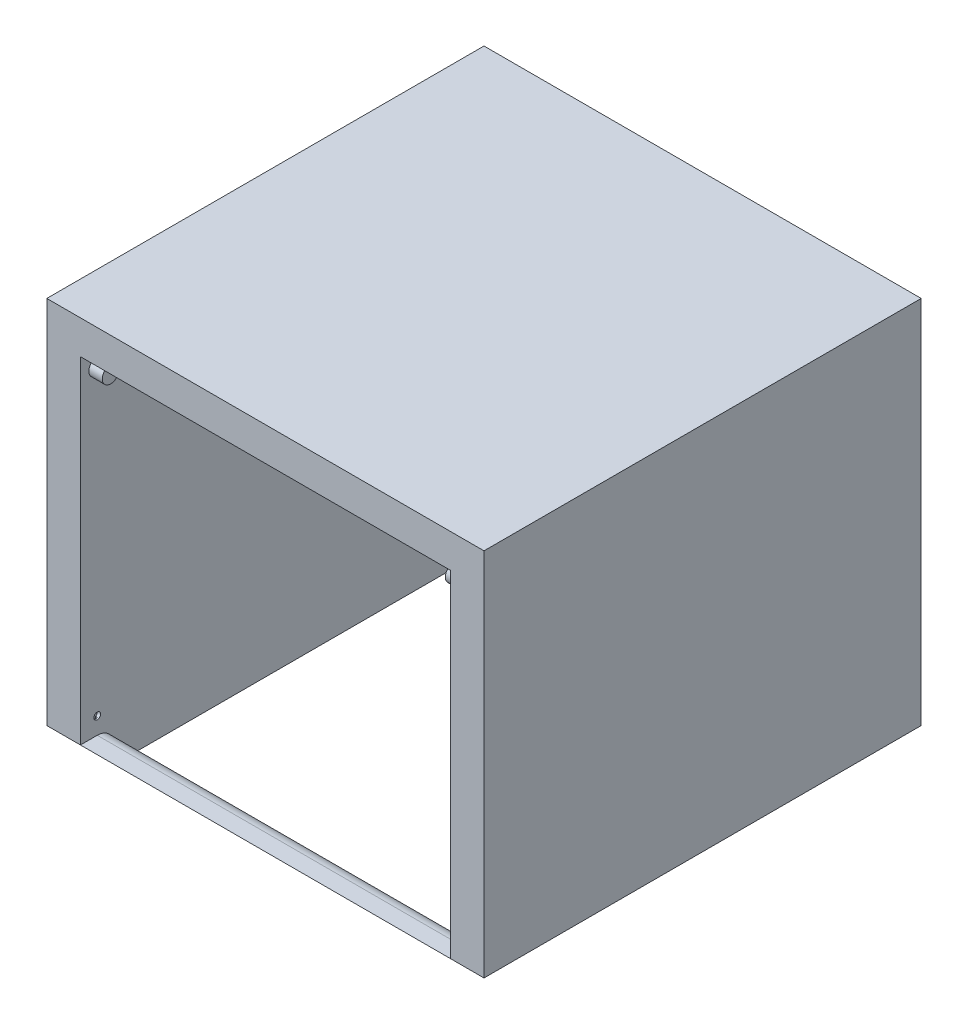
SolidWorks part; units mm, degrees
ref_plane "Front Plane" through (0, 0, 0) normal (0, 0, 1) x (1, 0, 0)
ref_plane "Top Plane" through (0, 0, 0) normal (0, 1, 0) x (1, 0, 0)
ref_plane "Right Plane" through (0, 0, 0) normal (1, 0, 0) x (0, 0, -1)
sketch "Sketch1" plane through (0, 0, 0) normal (0, 1, 0) x (1, 0, 0)
  line L0 (-325, 325) -> (-325, -325)
  line L1 (225, 225) -> (-225, 225)
  line L2 (225, 225) -> (225, -225)
  line L3 (225, -225) -> (-225, -225)
  line L4 (-225, 225) -> (-225, -225)
  line L5 (225, 225) -> (-225, -225) construction
  line L6 (225, -225) -> (-225, 225) construction
  line L7 (325, -325) -> (-325, -325)
  line L8 (325, 325) -> (325, -325)
  line L9 (325, 325) -> (-325, 325)
  point P0 (0, 0)
  dimension "D1" = 450
  dimension "D2" = 450
  dimension "D3" = 100
extrude "Boss-Extrude2" add sketch "Sketch1" against normal blind 103 draft 45
sketch "Sketch5" plane through (0, 0, 0) normal (0, 1, 0) x (1, 0, 0)
  line L0 (-275, -275) -> (-275, 275)
  line L1 (-225, -225) -> (225, -225)
  line L2 (-225, -225) -> (-225, 225)
  line L3 (-225, 225) -> (225, 225)
  line L4 (225, -225) -> (225, 225)
  line L5 (-275, 275) -> (275, 275)
  line L6 (275, -275) -> (275, 275)
  line L7 (-275, -275) -> (275, -275)
  dimension "D1" = 50
extrude "Cut-Extrude2" cut sketch "Sketch5" against normal blind 103
sketch "Sketch7" plane through (0, 0, 0) normal (0, 1, 0) x (1, 0, 0)
  line L0 (-275, 275) -> (-275, -325)
  line L1 (-325, -325) -> (-275, -325)
  line L2 (-325, -325) -> (-325, 325)
  line L3 (-325, 325) -> (325, 325)
  line L4 (325, -325) -> (325, 325)
  line L5 (275, 275) -> (-275, 275)
  line L9 (275, 275) -> (275, -325)
  line L10 (275, -325) -> (325, -325)
extrude "Boss-Extrude3" add sketch "Sketch7" along normal blind 500
sketch "Sketch8" plane through (0, 500, 0) normal (0, 1, 0) x (1, 0, 0)
  line L1 (-325, -325) -> (325, -325)
  line L2 (-325, -325) -> (-325, 325)
  line L3 (-325, 325) -> (325, 325)
  line L4 (325, -325) -> (325, 325)
extrude "Boss-Extrude4" add sketch "Sketch8" along normal blind 50
fillet "Fillet1" radius 25 1 edges at (0, 0, 275)
sketch "Sketch9" plane through (-275, 0, 0) normal (1, 0, 0) x (0, 0, -1)
  line L0 (-325, 500) -> (-275, 450) construction
  line L1 (-325, 550) -> (-325, 0) construction
  circle A0 centre (-300, 475) radius 12.5
  dimension "D3" = 25
  dimension "D1" = 50
  dimension "D2" = 45
extrude "Boss-Extrude5" add sketch "Sketch9" along normal blind 20
mirror "Mirror1" about plane through (0, 0, 0) normal (1, 0, 0) of "Boss-Extrude5"
sketch "Sketch10" plane through (-275, 0, 0) normal (1, 0, 0) x (0, 0, -1)
  line L0 (-325, 0) -> (-275, 50) construction
  line L1 (-325, 500) -> (-325, 0) construction
  line L2 (-300, 25) -> (-325, 25) construction
  line L3 (-325, 550) -> (-325, 0) construction
  circle A0 centre (-300, 25) radius 5
  dimension "D3" = 10
  dimension "D1" = 45
  dimension "D2" = 50
extrude "Cut-Extrude3" cut sketch "Sketch10" against normal blind 5
sketch "Sketch11" plane through (0, 0, 0) normal (0, 1, 0) x (1, 0, 0)
  line L0 (-325, -325) -> (-280, -325) construction
  line L1 (-325, -325) -> (-275, -325) construction
  line L2 (-280, -325) -> (-280, -300) construction
  line L3 (-280, -300) -> (-280, -302.5) construction
  line L5 (-280, -302.5) -> (-277.5, -302.5)
  line L6 (-280, -302.5) -> (-280, -297.5)
  line L7 (-280, -297.5) -> (-277.5, -297.5)
  line L8 (-277.5, -302.5) -> (-277.5, -297.5)
  dimension "D1" = 45
  dimension "D2" = 25
  dimension "D3" = 2.5
  dimension "D4" = 5
  dimension "D5" = 2.5
extrude "Cut-Extrude4" cut sketch "Sketch11" against normal through all
extrude "Cut-Extrude5" cut sketch "Sketch11<2>" along normal blind 25
sketch "Sketch11<2>" plane through (0, 0, 0) normal (0, 1, 0) x (1, 0, 0) same geometry as "Sketch11"
sketch "Sketch13" plane through (0, 0, -275) normal (0, 0, 1) x (1, 0, 0)
  line L0 (-275, 0) -> (275, 0) construction
  line L1 (-275, 500) -> (-270, 500)
  line L2 (-275, 500) -> (-275, 0)
  line L3 (-275, 0) -> (-270, 0)
  line L4 (-270, 500) -> (-270, 0)
  dimension "D1" = 5
extrude "Cut-Extrude6" cut sketch "Sketch13" against normal blind 5
sketch "Sketch14" plane through (0, -162.5, 162.5) normal (0, -0.7071, 0.7071) x (1, 0, 0)
  line L0 (-302.5, 197.9899) -> (-297.5, 190.9188)
  line L1 (-280, 197.9899) -> (-302.5, 197.9899)
  line L2 (-280, 197.9899) -> (-280, 190.9188)
  line L3 (-280, 190.9188) -> (-297.5, 190.9188)
extrude "Cut-Extrude7" cut sketch "Sketch14" against normal blind 2.5
sketch "Sketch18" plane through (-162.5, -162.5, 0) normal (-0.7071, -0.7071, 0) x (0, 0, 1)
  line L0 (302.5, 197.9899) -> (297.5, 190.9188)
  line L1 (-275, 190.9188) -> (-275, 197.9899)
  line L3 (297.5, 190.9188) -> (-275, 190.9188)
  line L4 (302.5, 197.9899) -> (-275, 197.9899)
extrude "Cut-Extrude11" cut sketch "Sketch18" against normal blind 2.5
sketch "Sketch19" plane through (-280, 0, 0) normal (-1, 0, 0) x (0, 0, 1)
  line L0 (297.5, -23.9645) -> (295.7322, -25.7322)
  line L1 (295.7322, -25.7322) -> (297.5, -27.5)
  line L2 (297.5, -27.5) -> (297.5, -23.9645)
extrude "Cut-Extrude12" cut sketch "Sketch19" against normal blind 2.5
fillet "Fillet2" radius 1.25 1 edges at (-278.75, -23.9645, 297.5)
fillet "Fillet3" radius 1.25 2 edges at (-280, -21.6161, 301.6161) (-280, -22.5314, 298.9331)
fillet "Fillet4" radius 1.25 1 edges at (-298.2322, -23.2322, 298.2322)
sketch "Sketch22" plane through (-140, 140, 0) normal (0.7071, -0.7071, 0) x (0, 0, -1)
  line L1 (-302.5, -229.8097) -> (-299.8483, -229.8097)
  line L2 (-302.5, -229.8097) -> (-302.5, -227.3097)
  line L3 (-302.5, -227.3097) -> (-299.8483, -227.3097)
  line L4 (-299.8483, -229.8097) -> (-299.8483, -227.3097)
extrude "Boss-Extrude6" add sketch "Sketch22" against normal blind 2.5
sketch "Sketch23" plane through (0, 140, 140) normal (0, -0.7071, -0.7071) x (1, 0, 0)
  line L0 (-281.25, 227.3097) -> (-299.8483, 227.3097) construction
  line L1 (-302.5, 229.8097) -> (-298.902, 229.8097)
  line L2 (-302.5, 229.8097) -> (-302.5, 227.3097)
  line L3 (-302.5, 227.3097) -> (-298.902, 227.3097)
  line L4 (-298.902, 229.8097) -> (-298.902, 227.3097)
extrude "Boss-Extrude7" add sketch "Sketch23" against normal blind 2.5
sketch "Sketch25" plane through (-162.5, -162.5, 0) normal (-0.7071, -0.7071, 0) x (0, 0, 1)
  line L1 (-275, 190.9188) -> (-280, 190.9188)
  line L2 (-275, 190.9188) -> (-275, 197.9899)
  line L4 (-280, 190.9188) -> (-280, 197.9899)
  line L5 (-275, 197.9899) -> (-280, 197.9899)
extrude "Cut-Extrude13" cut sketch "Sketch25" against normal blind 39
sketch "Sketch26" plane through (0, 0, -280) normal (0, 0, 1) x (1, 0, 0)
  line L1 (-270, 0.1543) -> (-269.8963, 0.1543)
  line L2 (-270, 0.1543) -> (-270, -0.0338)
  line L3 (-270, -0.0338) -> (-269.8963, -0.0338)
  line L4 (-269.8963, 0.1543) -> (-269.8963, -0.0338)
extrude "Boss-Extrude8" add sketch "Sketch26" along normal blind 5
sketch "Sketch27" plane through (0, 500, 0) normal (0, -1, 0) x (1, 0, 0)
  line L0 (-275, 275) -> (275, -275) construction
  line L2 (-42.5, -27) -> (42.5, -27)
  line L3 (-42.5, -27) -> (-42.5, 27)
  line L4 (-42.5, 27) -> (42.5, 27)
  line L5 (42.5, -27) -> (42.5, 27)
  line L6 (-42.5, -27) -> (42.5, 27) construction
  line L7 (-42.5, 27) -> (42.5, -27) construction
  point P4 (0, 0)
  dimension "D1" = 85
  dimension "D2" = 54
extrude "Cut-Extrude14" cut sketch "Sketch27" against normal blind 40
sketch "Sketch28" plane through (0, 500, 0) normal (0, -1, 0) x (1, 0, 0)
  line L0 (-42.5, -27) -> (42.5, -27) construction
  line L1 (-42.5, 27) -> (-57.5, 27)
  line L2 (-42.5, 27) -> (-42.5, -27)
  line L3 (-42.5, -27) -> (-57.5, -27)
  line L4 (-57.5, 27) -> (-57.5, -27)
  dimension "D1" = 0
  dimension "D2" = 15
extrude "Cut-Extrude15" cut sketch "Sketch28" against normal blind 10
sketch "Sketch29" plane through (0, 0, -27) normal (0, 0, 1) x (1, 0, 0)
  line L0 (-42.5, 500) -> (-27.5, 500) construction
  line L1 (-275, 500) -> (275, 500) construction
  line L2 (-7.5, 515) -> (-7.5, 510)
  line L3 (-27.5, 500) -> (-22.5, 500)
  line L4 (-27.5, 500) -> (-27.5, 515)
  line L13 (-7.5, 510) -> (-10, 510)
  line L15 (-22.5, 520) -> (-12.5, 520)
  line L16 (-22.5, 500) -> (-22.5, 515)
  line L17 (-22.5, 515) -> (-12.5, 515)
  line L18 (-12.5, 515) -> (-12.5, 512.5)
  line L19 (-22.5, 500) -> (17.5, 500) construction
  line L20 (-22.5, 510) -> (22.5, 510) construction
  line L21 (32.4362, 514.9178) -> (32.4362, 509.9178)
  line L22 (12.4362, 499.9178) -> (17.4362, 499.9178)
  line L23 (12.4362, 499.9178) -> (12.4362, 514.9178)
  line L24 (32.4362, 509.9178) -> (29.9362, 509.9178)
  line L25 (17.4362, 519.9178) -> (27.4362, 519.9178)
  line L26 (17.4362, 499.9178) -> (17.4362, 514.9178)
  line L27 (17.4362, 514.9178) -> (27.4362, 514.9178)
  line L28 (27.4362, 514.9178) -> (27.4362, 512.4178)
  arc A0 (-12.5, 520) -> (-7.5, 515) centre (-12.5, 515) cw
  arc A2 (-27.5, 515) -> (-22.5, 520) centre (-22.5, 515) cw
  arc A3 (27.4362, 519.9178) -> (32.4362, 514.9178) centre (27.4362, 514.9178) cw
  arc A4 (12.4362, 514.9178) -> (17.4362, 519.9178) centre (17.4362, 514.9178) cw
  arc A5 (29.9362, 509.9178) -> (27.4362, 512.4178) centre (29.9362, 512.4178) cw
  arc A6 (-10, 510) -> (-12.5, 512.5) centre (-10, 512.5) cw
  point P29 (27.4362, 509.9178)
  point P32 (-12.5, 510)
  dimension "D3" = 5
  dimension "D11" = 5
  dimension "D15" = 2.5
  dimension "D1" = 15
  dimension "D2" = 5
  dimension "D4" = 5
  dimension "D5" = 5
  dimension "D6" = 40
  dimension "D7" = 15
  dimension "D8" = 10
  dimension "D9" = 45
  dimension "D10" = 5
  dimension "D12" = 5
  dimension "D13" = 15
  dimension "D14" = 10
extrude "Cut-Extrude16" cut sketch "Sketch29" against normal blind 5
mirror "Mirror2" about plane through (0, 0, 0) normal (0, 0, 1) of "Cut-Extrude16"
fillet "Fillet5" radius 10 1 edges at (-42.5, 510, 0)
